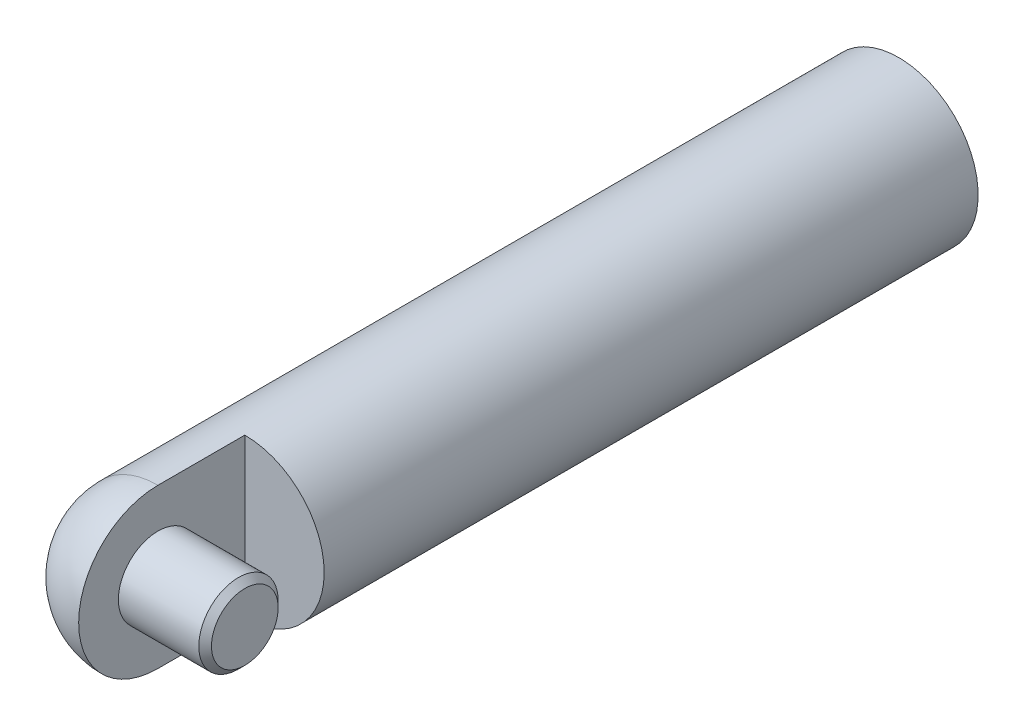
SolidWorks part; units mm, degrees
ref_plane "Front Plane" through (0, 0, 0) normal (1, 0, 0) x (0, 1, 0)
ref_plane "Top Plane" through (0, 0, 0) normal (0, 0, 1) x (0, 1, 0)
ref_plane "Right Plane" through (0, 0, 0) normal (0, 1, 0) x (-1, 0, 0)
sketch "Sketch1" plane through (0, 0, 0) normal (1, 0, 0) x (0, 1, 0)
  line L0 (0, 0) -> (-19.05, 0)
  line L1 (-19.05, 0) -> (-19.05, 177.8)
  line L2 (0, 0) -> (0, 177.8)
  line L3 (0, 177.8) -> (0, 196.85)
  arc A0 (-19.05, 177.8) -> (0, 196.85) centre (0, 177.8) cw
  dimension "D1" = 177.8
  dimension "D2" = 19.05
revolve "Revolve1" add sketch "Sketch1" angle 360 about L2
sketch "Sketch2" plane through (0, 0, 0) normal (1, 0, 0) x (0, 1, 0)
  line L0 (19.05, 177.8) -> (-19.05, 177.8) construction
  line L1 (19.05, 177.8) -> (-19.05, 177.8)
  line L2 (19.05, 0) -> (19.05, 177.8) construction
  line L4 (-19.05, 177.8) -> (-19.05, 0) construction
  line L5 (19.05, 0) -> (19.05, 177.8)
  line L6 (-19.05, 177.8) -> (-19.05, 0)
  line L7 (-19.05, 156.972) -> (19.05, 156.972)
  circle A0 centre (0, 177.8) radius 9.525
  arc A1 (19.05, 177.8) -> (-19.05, 177.8) centre (0, 177.8) ccw construction
  arc A2 (19.05, 177.8) -> (-19.05, 177.8) centre (0, 177.8) ccw
  dimension "D1" = 19.05
  dimension "D2" = 20.828
extrude "Cut-Extrude2" cut sketch "Sketch2" along normal through all contours A0 L1 L6 L7 L5 | L1 A2 A0 | L1 A0 | L1 A0 region at (0, 0, 165.9913) region at (0, 14.2875, 178.226) region at (0, 0, 173.7575) region at (0, 0, 181.8425)
extrude "Boss-Extrude1" add sketch "Sketch2<4>" along normal blind 20.828 contours L1 A0 | L1 A0 region at (0, 0, 173.7575) region at (0, 0, 181.8425)
sketch "Sketch2<4>" plane through (0, 0, 0) normal (1, 0, 0) x (0, 1, 0) same geometry as "Sketch2"
chamfer "Chamfer1" distance 1.524 angle 45 1 edges at (20.828, 0, 168.275)
